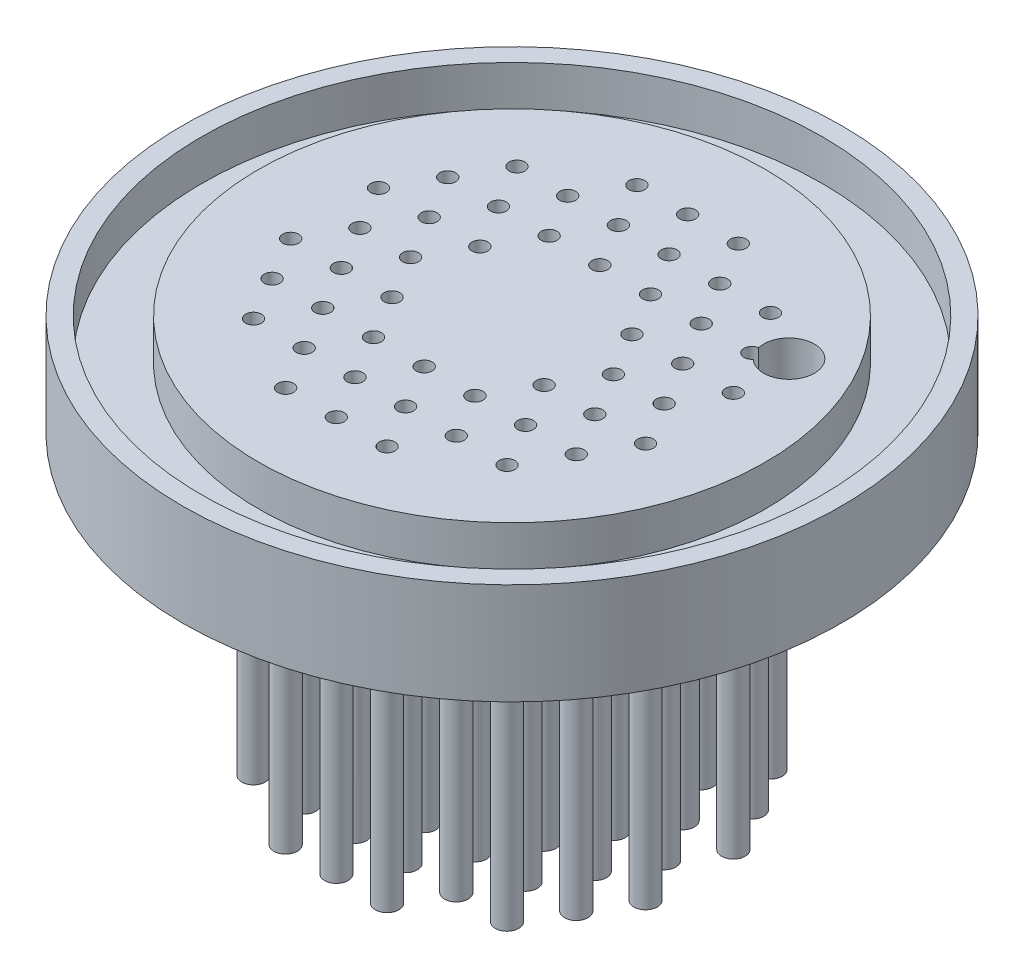
SolidWorks part; units mm, degrees
ref_plane "Front Plane" through (0, 0, 0) normal (0, 0, 1) x (1, 0, 0)
ref_plane "Top Plane" through (0, 0, 0) normal (0, 1, 0) x (1, 0, 0)
ref_plane "Right Plane" through (0, 0, 0) normal (1, 0, 0) x (0, 0, -1)
sketch "Sketch1" plane through (0, 0, 0) normal (0, 0, 1) x (1, 0, 0)
  line L0 (-15.875, 6.35) -> (-15.875, 3.81)
  line L1 (0, 0) -> (-20.6375, 0)
  line L2 (0, 0) -> (0, 6.35)
  line L3 (0, 6.35) -> (-15.875, 6.35)
  line L4 (-20.6375, 0) -> (-20.6375, 6.35)
  line L5 (-15.875, 3.81) -> (-19.431, 3.81)
  line L6 (-19.431, 3.81) -> (-19.431, 6.35)
  line L7 (-19.431, 6.35) -> (-20.6375, 6.35)
  dimension "D1" = 6.35
  dimension "D2" = 20.6375
  dimension "D3" = 2.54
  dimension "D4" = 3.556
  dimension "D5" = 15.875
revolve "Revolve1" add sketch "Sketch1" angle 360 about L2
hole_wizard "1/8 (0.125) Diameter Hole1" positions "Sketch8" profile "Sketch7" hole size "1/8" standard "ANSI Inch" end condition through all
sketch "Sketch8" plane through (0, 6.35, 0) normal (0, 1, 0) x (1, 0, 0)
  line L0 (0, 0) -> (10.9985, 6.35) construction
  line L2 (0, 0) -> (46.6204, 0) construction
  point P0 (10.9985, 6.35)
  dimension "D1" = 30
  dimension "D2" = 12.7
sketch "Sketch7" plane through (10.9985, 6.35, -6.35) normal (1, 0, 0) x (0, 0, 1)
  line L0 (0, 0) -> (0, 6.35)
  line L1 (0, 6.35) -> (1.5875, 6.35)
  line L2 (1.5875, 6.35) -> (1.5875, 0)
  line L5 (1.5875, 0) -> (0, 0)
  line L11 (0, -6.35) -> (0, 107.95) construction
  dimension "Thru Hole Dia." = 3.175
  dimension "Thru Hole Depth" = 6.35
sketch "Sketch9" plane through (0, 0, 0) normal (0, -1, 0) x (1, 0, 0)
  line L0 (0, 5.4993) -> (1.5875, 8.2489) construction
  line L1 (1.5875, 8.2489) -> (3.175, 10.9985) construction
  line L2 (3.175, 10.9985) -> (0, 10.9985) construction
  line L3 (0, 10.9985) -> (-3.175, 10.9985) construction
  line L4 (-3.175, 10.9985) -> (-4.7625, 8.2489) construction
  line L5 (-4.7625, 8.2489) -> (-3.175, 5.4993) construction
  line L6 (-3.175, 5.4993) -> (0, 5.4993) construction
  line L7 (0, 5.4993) -> (-1.5875, 8.2489) construction
  line L8 (-1.5875, 8.2489) -> (-3.175, 5.4993) construction
  line L9 (-4.7625, 8.2489) -> (-1.5875, 8.2489) construction
  line L10 (-1.5875, 8.2489) -> (-3.175, 10.9985) construction
  line L11 (0, 10.9985) -> (-1.5875, 8.2489) construction
  line L12 (-1.5875, 8.2489) -> (1.5875, 8.2489) construction
  line L13 (1.5875, 8.2489) -> (0, 10.9985) construction
  line L14 (-3.175, 5.4993) -> (0, 0) construction
  line L15 (0, 0) -> (0, 5.4993) construction
  circle A0 centre (0, 0) radius 12.7 construction
  circle A1 centre (0, 0) radius 31.75 construction
  circle A2 centre (3.175, 10.9985) radius 0.7366
  circle A3 centre (3.175, 10.9985) radius 0.4953
  circle A4 centre (0, 10.9985) radius 0.4953
  circle A5 centre (0, 10.9985) radius 0.7366
  circle A8 centre (-3.175, 10.9985) radius 0.4953 [skipped]
  circle A9 centre (-3.175, 10.9985) radius 0.7366 [skipped]
  circle A10 centre (1.5875, 8.2489) radius 0.4953
  circle A11 centre (1.5875, 8.2489) radius 0.7366
  circle A12 centre (0, 5.4993) radius 0.4953
  circle A13 centre (0, 5.4993) radius 0.7366
  circle A14 centre (-3.175, 5.4993) radius 0.4953
  circle A15 centre (-3.175, 5.4993) radius 0.7366
  circle A16 centre (-4.7625, 8.2489) radius 0.4953
  circle A17 centre (-4.7625, 8.2489) radius 0.7366
  circle A18 centre (-3.175, 10.9985) radius 0.4953
  circle A19 centre (-3.175, 10.9985) radius 0.7366
  circle A20 centre (-1.5875, 8.2489) radius 0.7366
  circle A21 centre (-1.5875, 8.2489) radius 0.4953
  point P4 (0, 5.4993)
  point P5 (0, 10.9985)
  point P6 (-1.5875, 8.2489)
  point P7 (1.5875, 8.2489)
  point P8 (3.175, 10.9985)
  point P9 (-3.175, 10.9985)
  point P10 (-4.7625, 8.2489)
  point P11 (-3.175, 5.4993)
  point P46 (-1.5875, 8.2489)
  dimension "D1" = 25.4
  dimension "D8" = 1.4732
  dimension "D9" = 0.9906
  dimension "D2" = 19.05
  dimension "D3" = 3.175
  dimension "D4" = 3.175
  dimension "D5" = 3.175
  dimension "D6" = 3.175
  dimension "D10" = 3
  dimension "D12" = 2
  dimension "D11" = 6
extrude "Boss-Extrude1" add sketch "Sketch9" along normal blind 18.415
ref_axis "Axis2" through (0, 7.5565, 0) along (0, -1, 0)
extrude "Cut-Extrude1" cut sketch "Sketch9<2>" against normal through all contours A3 | A10 | A21 | A4 | A14 | A12 | A16 | A18
sketch "Sketch9<2>" plane through (0, 0, 0) normal (0, -1, 0) x (1, 0, 0) same geometry as "Sketch9"
pattern_circular "CirPattern4" count 6 over 360 about axis through (0, 7.5565, 0) along (0, -1, 0) of "Boss-Extrude1", "Cut-Extrude1"
equation "\"D4@Sketch9\"=\"D3@Sketch9\""
equation "\"D5@Sketch9\"=\"D3@Sketch9\""
equation "\"D6@Sketch9\"=\"D3@Sketch9\""
